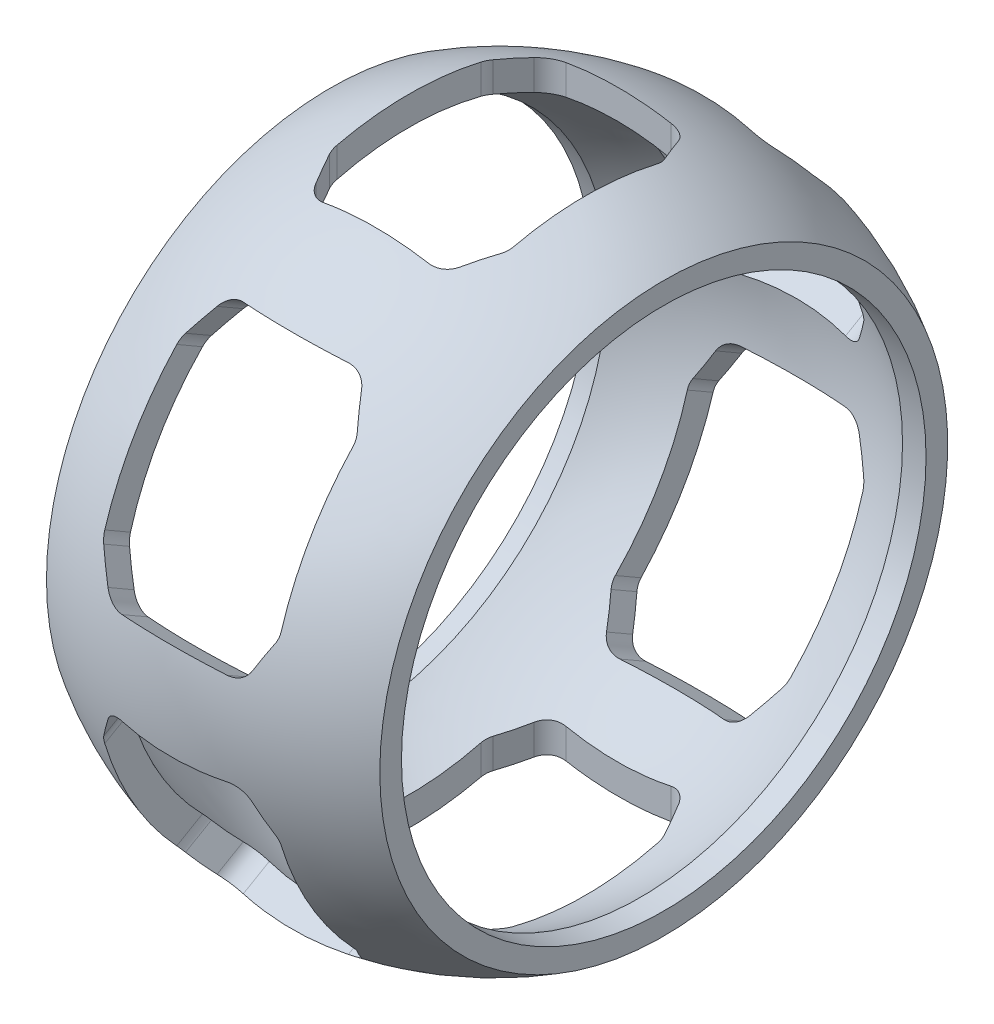
SolidWorks part; units mm, degrees
ref_plane "Front Plane" through (0, 0, 0) normal (0, 0, 1) x (1, 0, 0)
ref_plane "Top Plane" through (0, 0, 0) normal (0, 1, 0) x (1, 0, 0)
ref_plane "Right Plane" through (0, 0, 0) normal (1, 0, 0) x (0, 0, -1)
sketch "Sketch2" plane through (0, 0, 0) normal (0, 1, 0) x (1, 0, 0)
  line L0 (0, 0) -> (129.0301, 0) construction
  line L1 (0, 0) -> (162, 0) construction
  line L2 (0, 25.7597) -> (0, 23.6145)
  line L3 (0, 23.6145) -> (1.5616, 23.6145)
  line L5 (30.2387, 25.7597) -> (30.2387, 23.7937)
  line L6 (30.2387, 23.7937) -> (28.1056, 23.7937)
  arc A0 (0, 25.7597) -> (30.2387, 25.7597) centre (15.1194, 0.5514) cw
  arc A1 (1.5616, 23.6145) -> (28.1056, 23.7937) centre (14.9786, 2.2257) cw
  point P11 (0, 0)
  point P13 (0, 23.138)
  point P15 (27.2099, 23.7981)
  point P16 (25.8728, 23.3591)
  point P17 (3.0548, 23.3591)
  point P18 (27.4465, 23.3591)
  point P19 (2.4651, 23.5016)
  point P20 (28.1056, 23.7937)
  point P21 (1.5616, 23.6145)
  dimension "D1" = 162
revolve "Revolve1" add sketch "Sketch2" angle 360 about L0
sketch "Sketch3" plane through (0, 0, 0) normal (0, 1, 0) x (1, 0, 0)
  line L0 (0, 0) -> (30.2387, 0) construction
  line L1 (30.2387, -25.7597) -> (30.2387, 25.7597) construction
  line L2 (7.3305, 7.4223) -> (8.5666, 9.8944)
  line L3 (10.3554, -11) -> (19.8833, -11)
  line L4 (7.1194, -6.5279) -> (7.1194, 6.5279)
  line L5 (10.3554, 11) -> (19.8833, 11)
  line L6 (23.1194, -6.5279) -> (23.1194, 6.5279)
  line L7 (7.1194, -11) -> (23.1194, 11) construction
  line L8 (7.1194, 11) -> (23.1194, -11) construction
  line L9 (21.6721, -9.8944) -> (22.9082, -7.4223)
  line L10 (21.6721, 9.8944) -> (22.9082, 7.4223)
  line L11 (7.3305, -7.4223) -> (8.5666, -9.8944)
  arc A0 (21.6721, -9.8944) -> (19.8833, -11) centre (19.8833, -9) cw
  arc A1 (22.9082, -7.4223) -> (23.1194, -6.5279) centre (21.1194, -6.5279) ccw
  arc A2 (22.9082, 7.4223) -> (23.1194, 6.5279) centre (21.1194, 6.5279) cw
  arc A3 (21.6721, 9.8944) -> (19.8833, 11) centre (19.8833, 9) ccw
  arc A4 (8.5666, 9.8944) -> (10.3554, 11) centre (10.3554, 9) cw
  arc A5 (7.3305, 7.4223) -> (7.1194, 6.5279) centre (9.1194, 6.5279) ccw
  arc A6 (8.5666, -9.8944) -> (10.3554, -11) centre (10.3554, -9) ccw
  arc A7 (7.3305, -7.4223) -> (7.1194, -6.5279) centre (9.1194, -6.5279) cw
  point P3 (15.1194, 0)
  point P6 (15.1194, 0)
  point P21 (21.1194, -11)
  point P24 (23.1194, -7)
  point P27 (23.1194, 7)
  point P30 (21.1194, 11)
  point P33 (9.1194, 11)
  point P36 (7.1194, 7)
  point P39 (9.1194, -11)
  point P42 (7.1194, -7)
  dimension "D1" = 22
  dimension "D11" = 2
  dimension "D2" = 16
  dimension "D3" = 4
  dimension "D4" = 2
  dimension "D5" = 2
  dimension "D6" = 4
  dimension "D7" = 2
  dimension "D8" = 4
  dimension "D9" = 2
  dimension "D10" = 4
extrude "Cut-Extrude1" cut sketch "Sketch3" against normal through all both and the other way through all
pattern_circular "CirPattern1" count 3 over 360 about axis through (30.2387, 0, 0) along (-1, 0, 0) of "Cut-Extrude1"
ref_plane "Plane1" through (15.1194, 0, 0) normal (-1, 0, 0) x (0, 0, 1)
sketch "Sketch4" plane through (15.1194, 0, 0) normal (-1, 0, 0) x (0, 0, 1)
  line L0 (0, -38.8939) -> (0, 38.8939)
  line L1 (48.9648, 28.2699) -> (-48.9648, -28.2699)
  line L2 (48.2057, -27.8316) -> (-48.2057, 27.8316)
  point P3 (-48.2057, -29.6102)
  point P6 (0, 0)
  point P7 (27.5889, 16.1852)
  point P8 (0, 0)
  point P10 (-24.9732, 14.4183)
  point P12 (0, 0)
  point P13 (0, 0)
  point P14 (0, 0)
  point P15 (0, 0)
  point P16 (0, 38.8939)
  dimension "D1" = 60
  dimension "D2" = 60
sketch "Sketch5" plane through (0, 0, 11) normal (0, 0, -1) x (-1, 0, 0)
  spline S0 degree 3 poles (186.661, 1958.9502) (148.3451, 399.8302) (73.5174, -27.8201) (-15.9038, -27.853) (-16.6995, -27.8187) (-57.076, -24.2951) (-108.2681, 68.2176) (1978.6222, -16.1249) knots -27.385822 -27.385822 -27.385822 -27.385822 0.5 0.5 0.75 0.75 13.168274 13.168274 13.168274 13.168274 only from (-10.3554, -27.4345) to (-19.8833, -27.4345) construction
  spline S1 degree 3 poles (-10.3554, -27.4345) (-11.9355, -27.7141) (-13.5202, -27.8521) (-15.9038, -27.853) (-16.6995, -27.8187) (-18.2931, -27.6797) (-19.0946, -27.574) (-19.8833, -27.4345) knots 0 0 0 0 0.5 0.5 0.75 0.75 1 1 1 1
sketch "Sketch6" plane through (0, 0, -11) normal (0, 0, 1) x (1, 0, 0)
  spline S0 degree 3 poles (216.8997, 1958.9502) (178.5838, 399.8302) (103.7561, -27.8201) (14.3349, -27.853) (13.5392, -27.8187) (-26.8373, -24.2951) (-78.0293, 68.2176) (2008.8609, -16.1249) knots -27.385822 -27.385822 -27.385822 -27.385822 0.5 0.5 0.75 0.75 13.168274 13.168274 13.168274 13.168274 only from (19.8833, -27.4345) to (10.3554, -27.4345) construction
  spline S1 degree 3 poles (19.8833, -27.4345) (18.3032, -27.7141) (16.7185, -27.8521) (14.3349, -27.853) (13.5392, -27.8187) (11.9456, -27.6797) (11.1441, -27.574) (10.3554, -27.4345) knots 0 0 0 0 0.5 0.5 0.75 0.75 1 1 1 1
ref_axis "Axis1" through (35.181, 0, 0) along (-1, 0, 0)
ref_plane "Plane2" through (0, 0, 0) normal (0, 0.866, -0.5) x (0, -0.5, -0.866)
sketch "Sketch7" plane through (0, 0, 0) normal (0, 0.866, -0.5) x (0, -0.5, -0.866)
  circle A0 centre (0, -15.1194) radius 33.6796
